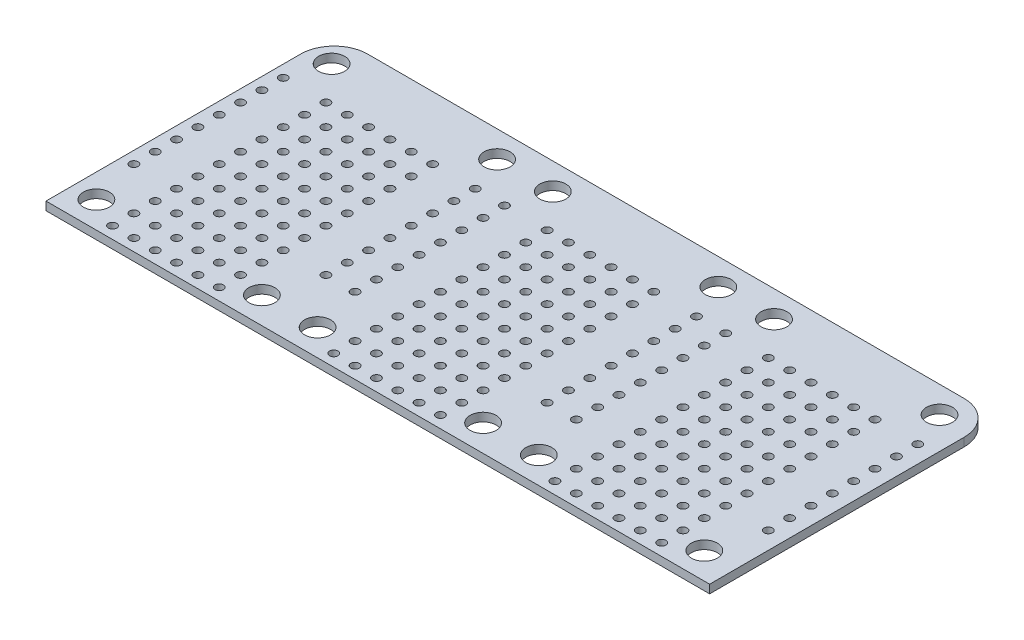
SolidWorks part; units mm, degrees
ref_plane "Front Plane" through (0, 0, 0) normal (0, 0, 1) x (1, 0, 0)
ref_plane "Top Plane" through (0, 0, 0) normal (0, 1, 0) x (1, 0, 0)
ref_plane "Right Plane" through (0, 0, 0) normal (1, 0, 0) x (0, 0, -1)
sketch "board" plane through (0, 0, 0) normal (0, 1, 0) x (1, 0, 0)
  line L1 (0, 0) -> (79, 0)
  line L2 (0, 0) -> (0, 34.3)
  line L3 (0, 34.3) -> (79, 34.3)
  line L4 (79, 0) -> (79, 34.3)
  dimension "D1" = 79
  dimension "D2" = 34.3
sketch "holes" plane through (0, 0, 0) normal (0, 1, 0) x (1, 0, 0)
  line L0 (0, 26.82) -> (1.42, 26.82) construction
  line L5 (1.42, 26.82) -> (6.5, 26.82) construction
  line L6 (2.85, 3.15) -> (22.55, 3.15) construction
  line L7 (22.55, 3.15) -> (22.55, 31.15) construction
  line L8 (22.55, 31.15) -> (2.85, 31.15) construction
  line L9 (2.85, 31.15) -> (2.85, 3.15) construction
  line L10 (12.7, 0) -> (12.7, 3.15) construction
  line L11 (6.5, 26.82) -> (6.5, 24.28) construction
  line L12 (6.5, 26.82) -> (9.04, 26.82) construction
  line L13 (1.42, 26.82) -> (24.28, 26.82) construction
  line L14 (0, 0) -> (2.85, 0) construction
  line L15 (2.85, 0) -> (2.85, 3.15) construction
  line L16 (2.85, 0) -> (12.7, 0) construction
  line L17 (1.42, 26.82) -> (1.42, 24.28) construction
  line L18 (0, 0) -> (0, 26.82) construction
  circle A0 centre (2.85, 31.15) radius 1.55
  circle A1 centre (22.55, 31.15) radius 1.55
  circle A2 centre (22.55, 3.15) radius 1.55
  circle A3 centre (2.85, 3.15) radius 1.55
  circle A4 centre (1.42, 26.82) radius 0.5
  circle A5 centre (24.28, 26.82) radius 0.5
  circle A6 centre (6.5, 26.82) radius 0.5
  circle A12 centre (1.42, 24.28) radius 0.5
  circle A13 centre (24.28, 24.28) radius 0.5
  circle A14 centre (1.42, 21.74) radius 0.5
  circle A15 centre (24.28, 21.74) radius 0.5
  circle A16 centre (1.42, 19.2) radius 0.5
  circle A17 centre (24.28, 19.2) radius 0.5
  circle A18 centre (1.42, 16.66) radius 0.5
  circle A19 centre (24.28, 16.66) radius 0.5
  circle A20 centre (1.42, 14.12) radius 0.5
  circle A21 centre (24.28, 14.12) radius 0.5
  circle A22 centre (1.42, 11.58) radius 0.5
  circle A23 centre (24.28, 11.58) radius 0.5
  circle A24 centre (1.42, 9.04) radius 0.5
  circle A25 centre (24.28, 9.04) radius 0.5
  circle A26 centre (6.5, 24.28) radius 0.5
  circle A27 centre (6.5, 21.74) radius 0.5
  circle A28 centre (6.5, 19.2) radius 0.5
  circle A29 centre (6.5, 16.66) radius 0.5
  circle A30 centre (6.5, 14.12) radius 0.5
  circle A31 centre (6.5, 11.58) radius 0.5
  circle A32 centre (6.5, 9.04) radius 0.5
  circle A33 centre (6.5, 6.5) radius 0.5
  circle A34 centre (6.5, 3.96) radius 0.5
  circle A35 centre (6.5, 1.42) radius 0.5
  circle A36 centre (9.04, 24.28) radius 0.5
  circle A37 centre (9.04, 21.74) radius 0.5
  circle A38 centre (9.04, 19.2) radius 0.5
  circle A39 centre (9.04, 16.66) radius 0.5
  circle A40 centre (9.04, 14.12) radius 0.5
  circle A41 centre (9.04, 11.58) radius 0.5
  circle A42 centre (9.04, 9.04) radius 0.5
  circle A43 centre (9.04, 6.5) radius 0.5
  circle A44 centre (9.04, 3.96) radius 0.5
  circle A45 centre (9.04, 1.42) radius 0.5
  circle A46 centre (11.58, 24.28) radius 0.5
  circle A47 centre (11.58, 21.74) radius 0.5
  circle A48 centre (11.58, 19.2) radius 0.5
  circle A49 centre (11.58, 16.66) radius 0.5
  circle A50 centre (11.58, 14.12) radius 0.5
  circle A51 centre (11.58, 11.58) radius 0.5
  circle A52 centre (11.58, 9.04) radius 0.5
  circle A53 centre (11.58, 6.5) radius 0.5
  circle A54 centre (11.58, 3.96) radius 0.5
  circle A55 centre (11.58, 1.42) radius 0.5
  circle A56 centre (14.12, 24.28) radius 0.5
  circle A57 centre (14.12, 21.74) radius 0.5
  circle A58 centre (14.12, 19.2) radius 0.5
  circle A59 centre (14.12, 16.66) radius 0.5
  circle A60 centre (14.12, 14.12) radius 0.5
  circle A61 centre (14.12, 11.58) radius 0.5
  circle A62 centre (14.12, 9.04) radius 0.5
  circle A63 centre (14.12, 6.5) radius 0.5
  circle A64 centre (14.12, 3.96) radius 0.5
  circle A65 centre (14.12, 1.42) radius 0.5
  circle A66 centre (16.66, 24.28) radius 0.5
  circle A67 centre (16.66, 21.74) radius 0.5
  circle A68 centre (16.66, 19.2) radius 0.5
  circle A69 centre (16.66, 16.66) radius 0.5
  circle A70 centre (16.66, 14.12) radius 0.5
  circle A71 centre (16.66, 11.58) radius 0.5
  circle A72 centre (16.66, 9.04) radius 0.5
  circle A73 centre (16.66, 6.5) radius 0.5
  circle A74 centre (16.66, 3.96) radius 0.5
  circle A75 centre (16.66, 1.42) radius 0.5
  circle A76 centre (19.2, 24.28) radius 0.5
  circle A77 centre (19.2, 21.74) radius 0.5
  circle A78 centre (19.2, 19.2) radius 0.5
  circle A79 centre (19.2, 16.66) radius 0.5
  circle A80 centre (19.2, 14.12) radius 0.5
  circle A81 centre (19.2, 11.58) radius 0.5
  circle A82 centre (19.2, 9.04) radius 0.5
  circle A83 centre (19.2, 6.5) radius 0.5
  circle A84 centre (19.2, 3.96) radius 0.5
  circle A85 centre (19.2, 1.42) radius 0.5
  circle A86 centre (9.04, 26.82) radius 0.5
  circle A87 centre (11.58, 26.82) radius 0.5
  circle A88 centre (14.12, 26.82) radius 0.5
  circle A89 centre (16.66, 26.82) radius 0.5
  circle A90 centre (19.2, 26.82) radius 0.5
  dimension "D6" = 3.1
  dimension "D7" = 1
  dimension "D10" = 22.86
  dimension "D2" = 2.85
  dimension "D3" = 19.7
  dimension "D4" = 28
  dimension "D5" = 1.42
  dimension "D8" = 3.15
  dimension "D9" = 5.08
  dimension "D11" = 26.82
  dimension "D12" = 8
  dimension "D14" = 2.54
  dimension "D17" = 2.54
  dimension "D18" = 2.54
  dimension "D15" = 11
  dimension "D16" = 6
extrude "Boss-Extrude1" add sketch "board" along normal blind 1
extrude "Cut-Extrude1" cut sketch "holes" along normal through all
pattern_linear "LPattern1" count 3 spacing 26.3333 along (1, 0, 0) of "Cut-Extrude1"
fillet "Fillet1" radius 4 2 edges at (79, 0.5, -34.3) (0, 0.5, -34.3)
ref_axis "Axis1" through (1.42, 1, -26.82) along (0, -1, 0)
ref_axis "Axis2" through (24.28, 1, -26.82) along (0, -1, 0)
ref_axis "Axis3" through (27.7533, 1, -26.82) along (0, -1, 0)
ref_axis "Axis4" through (50.6133, 1, -26.82) along (0, -1, 0)
ref_axis "Axis5" through (54.0867, 1, -26.82) along (0, -1, 0)
ref_axis "Axis6" through (76.9467, 1, -26.82) along (0, -1, 0)
ref_axis "Axis7" through (2.85, 1, -31.15) along (0, -1, 0)
ref_axis "Axis8" through (22.55, 1, -31.15) along (0, -1, 0)
ref_axis "Axis9" through (29.1833, 1, -31.15) along (0, -1, 0)
ref_axis "Axis10" through (48.8833, 1, -31.15) along (0, -1, 0)
ref_axis "Axis11" through (55.5167, 1, -31.15) along (0, -1, 0)
ref_axis "Axis12" through (75.2167, 1, -31.15) along (0, -1, 0)
ref_plane "Mid" through (39.5, 0, 0) normal (1, 0, 0) x (0, 0, -1)
